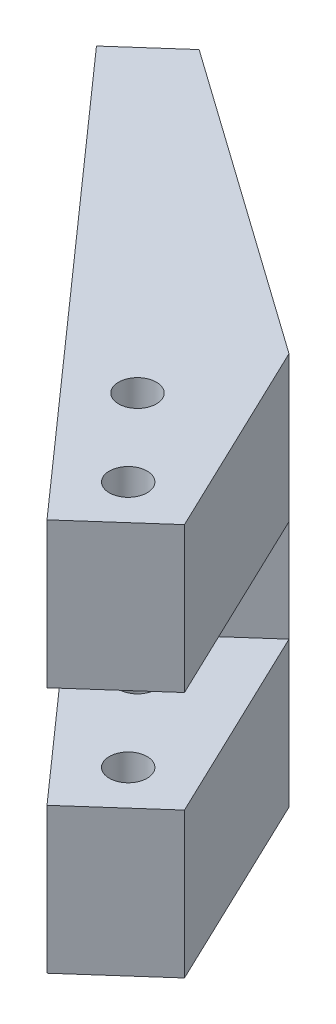
SolidWorks part; units mm, degrees
ref_plane "Front Plane" through (0, 0, 0) normal (0, 0, 1) x (1, 0, 0)
ref_plane "Top Plane" through (0, 0, 0) normal (0, 1, 0) x (1, 0, 0)
ref_plane "Right Plane" through (0, 0, 0) normal (1, 0, 0) x (0, 0, -1)
sketch "Sketch1" plane through (0, 0, 0) normal (0, 1, 0) x (1, 0, 0)
  line L0 (47.5, -78.4427) -> (47.5, -38.4427)
  line L1 (42.5, 50) -> (0, 0)
  line L2 (0, 0) -> (35.1, -73.4224)
  line L3 (47.5, 38.4427) -> (47.5, 50)
  line L4 (42.5, 50) -> (47.5, 50)
  line L6 (35.1, -73.4224) -> (35.1, -93.4427)
  line L8 (37.5, -78.4427) -> (37.5, -93.4427) construction
  line L9 (37.5, -93.4427) -> (47.5, -93.4427)
  line L10 (47.5, -78.4427) -> (47.5, -93.4427)
  line L11 (35.1, -93.4427) -> (37.5, -93.4427)
  line L12 (35.1, -73.4224) -> (37.5, -78.4427) construction
  arc A0 (47.5, 38.4427) -> (47.5, -38.4427) centre (65.622, 0) ccw
  dimension "D1" = 85
  dimension "D2" = 50
  dimension "D3" = 40
  dimension "D4" = 47.5
  dimension "D5" = 10
  dimension "D6" = 5
  dimension "D7" = 65.622
  dimension "D8" = 15
  dimension "D9" = 12.4
extrude "Boss-Extrude1" add sketch "Sketch1" along normal blind 14
sketch "Sketch3" plane through (0, 0, 0) normal (0, -1, 0) x (1, 0, 0)
  line L8 (36.1851, 83.429) -> (36.1851, 109.2435) construction
  line L9 (33.255, 84.4031) -> (36.1851, 92.429)
  line L10 (35.3457, 53.1123) -> (33.255, 84.4031)
  line L11 (46.1351, 70.029) -> (44.8209, 53.0622)
  line L12 (46.1351, 88.029) -> (46.1351, 70.029)
  line L13 (44.8851, 92.429) -> (46.1351, 88.029)
  line L14 (36.1851, 92.429) -> (44.8851, 92.429)
  circle A6 centre (40.0851, 83.429) radius 6.75 construction
  circle A7 centre (40.0851, 83.429) radius 4.125
  circle A8 centre (40.0851, 63.429) radius 1.5 construction
  circle A9 centre (40.0851, 58.929) radius 1.5 construction
  circle A10 centre (40.0851, 53.429) radius 1.5 construction
  arc A11 (44.8209, 53.0622) -> (35.3457, 53.1123) centre (40.0851, 53.429) cw
  point P48 (33.3351, 83.429)
  dimension "D6" = 108.929
  dimension "D7" = 113.429
  dimension "D1" = 3
  dimension "D2" = 40.0851
  dimension "D3" = 47.5
  dimension "D4" = 50
  dimension "D5" = 103.429
extrude "Cut-Extrude1" cut sketch "Sketch3" against normal blind 6
sketch "Sketch5" plane through (0, 6, 0) normal (0, -1, 0) x (1, 0, 0)
  circle A0 centre (40.0851, 63.429) radius 1.125
  circle A1 centre (40.0851, 58.929) radius 1.125
  circle A2 centre (40.0851, 53.429) radius 1.125
  circle A3 centre (40.0851, 63.429) radius 1.5 construction
  circle A4 centre (40.0851, 58.929) radius 1.5 construction
  circle A5 centre (40.0851, 53.429) radius 1.5 construction
  dimension "D1" = 2.25
extrude "Cut-Extrude2" cut sketch "Sketch5" against normal blind 15
fillet "Fillet1" radius 1 14 edges at (47.5, 7, 38.4427) (47.5, 7, -38.4427) (47.5, 7, -50) (42.5, 7, -50) (21.25, 14, -25) (45, 14, -50) (47.5, 14, -44.2214) (23.122, 14, 0) (47.5, 14, 65.9427) (21.25, 0, -25) (45, 0, -50) (47.5, 0, -44.2214) (23.122, 0, 0) (47.5, 0, 65.9427)
sketch "Sketch6" plane through (0, 0, 0) normal (0, -1, 0) x (1, 0, 0)
  line L0 (-40.4586, -20.0772) -> (-49.8876, -23.408)
  line L2 (0, 0) -> (34.1249, 71.3827)
  line L5 (-49.8876, -23.408) -> (34.1249, 71.3827)
  line L6 (-40.4586, -20.0772) -> (-20.5602, 2.374)
  arc A0 (0, 0) -> (-20.5602, 2.374) centre (-20.6309, -88.4563) ccw
  dimension "D1" = 10
  dimension "D2" = 30
  dimension "D3" = 16
extrude "Boss-Extrude3" add sketch "Sketch6" along normal blind 20 and the other way blind 34
sketch "Sketch7" plane through (-16.3209, 0, 14.4651) normal (-0.7484, 0, 0.6633) x (0.6633, 0, 0.7484)
  line L0 (76.0552, 14) -> (29.3477, 14)
  line L1 (76.0552, 0) -> (29.3477, 0)
  line L2 (29.3477, 34) -> (76.0552, 34)
  line L3 (76.0552, 34) -> (76.0552, 14)
  line L4 (29.3477, -20) -> (76.0552, -20)
  line L5 (76.0552, -20) -> (76.0552, 0)
  line L6 (76.0552, 34) -> (-50.6072, 34) construction
  line L7 (76.0552, 34) -> (76.0552, 14) construction
  line L8 (76.0552, 0) -> (76.0552, -20) construction
  line L9 (76.0552, -20) -> (-50.6072, -20) construction
  line L10 (29.3477, 14) -> (29.3477, 34)
  line L11 (29.3477, 0) -> (29.3477, -20)
  line L12 (1.0529, 14) -> (76.0552, 14) construction
extrude "Cut-Extrude3" cut sketch "Sketch7" against normal blind 30
sketch "Sketch10" plane through (0, -20, 0) normal (0, -1, 0) x (1, 0, 0)
  line L1 (-49.8876, -23.408) -> (-42.4038, -30.0408)
  line L2 (-49.8876, -23.408) -> (-16.7236, 14.0107)
  line L3 (-16.7236, 14.0107) -> (0, 0)
  line L4 (-42.4038, -30.0408) -> (0, 0)
  line L7 (3.1449, 36.4281) -> (-49.8876, -23.408) construction
  dimension "D1" = 10
  dimension "D2" = 90
  dimension "D3" = 50
extrude "Boss-Extrude4" add sketch "Sketch10" against normal blind 3
extrude "Boss-Extrude5" add sketch "Sketch10<2>" along normal blind 3 from surface starting at face at (-15.7543, 34, 3.9082)
sketch "Sketch10<2>" plane through (0, -20, 0) normal (0, -1, 0) x (1, 0, 0) same geometry as "Sketch10"
ref_plane "Plane2" through (0, 7, 0) normal (0, -1, 0) x (-1, 0, 0)
sketch "Sketch15" plane through (0, 6, 0) normal (0, -1, 0) x (-1, 0, 0)
  line L1 (-30.98, -71.3827) -> (-57.8606, -71.3827)
  line L2 (-30.98, -71.3827) -> (-30.98, -112.2395)
  line L3 (-30.98, -112.2395) -> (-57.8606, -112.2395)
  line L4 (-57.8606, -71.3827) -> (-57.8606, -112.2395)
extrude "Cut-Extrude5" cut sketch "Sketch15" along normal up to surface (6 mm away) up to face at (40.0851, 0, 87.554)
sketch "Sketch16" plane through (0, 14, 0) normal (0, 1, 0) x (1, 0, 0)
  circle A0 centre (40.0851, -83.429) radius 1.6
  circle A1 centre (40.0851, -63.429) radius 1.125 construction
  dimension "D1" = 20
  dimension "D2" = 3.2
extrude "Cut-Extrude6" cut sketch "Sketch16" against normal up to next
sketch "Sketch17" plane through (0, 7, 0) normal (0, -1, 0) x (-1, 0, 0)
  circle A0 centre (-22.3948, -50.6094) radius 103.4568 construction
sketch "Sketch19" plane through (-16.3209, 0, 14.4651) normal (-0.7484, 0, 0.6633) x (0.6633, 0, 0.7484)
  line L0 (29.3477, 14) -> (76.0552, 14) construction
  line L1 (0, 14) -> (109.6521, 14)
  line L2 (0, 14) -> (0, 0)
  line L3 (0, 0) -> (109.6521, 0)
  line L4 (109.6521, 14) -> (109.6521, 0)
  line L5 (76.0552, 0) -> (29.3477, 0) construction
  line L7 (0, 31) -> (0, 13) construction
extrude "Cut-Extrude7" cut sketch "Sketch19" against normal through all both and the other way through all
sketch "Sketch21" plane through (0, 0, 0) normal (0.9022, 0, -0.4313) x (-0.4313, 0, -0.9022)
  line L1 (-23.655, 14) -> (73.0722, 14)
  line L2 (-23.655, 14) -> (-23.655, 0)
  line L3 (-23.655, 0) -> (73.0722, 0)
  line L4 (73.0722, 14) -> (73.0722, 0)
  line L5 (0, 14) -> (-30.5304, 14) construction
  line L6 (0, 0) -> (-30.5304, 0) construction
  point P6 (0, 0)
extrude "Cut-Extrude8" cut sketch "Sketch21" along normal through all
sketch "Sketch22" plane through (0, -20, 0) normal (0, -1, 0) x (-1, 0, 0)
  line L0 (-3.1449, -36.4281) -> (49.8876, 23.408) construction
  line L2 (0, 0) -> (16.3209, -14.4651) construction
  line L3 (5.7335, -15.1033) -> (-8.7577, -31.4536) construction
  line L4 (-3.1449, -36.4281) -> (-13.1679, -27.5448) construction
  circle A0 centre (5.7335, -15.1033) radius 2.6
  circle A1 centre (-4.2157, -26.3289) radius 2.6
  point P6 (0, 0)
  dimension "D1" = 5.2
  dimension "D4" = 15
  dimension "D2" = 7.5
  dimension "D3" = 7.5
extrude "Cut-Extrude9" cut sketch "Sketch22" against normal through all contours A0 | A1
equation "\"A\"= 20mm"
equation "\"B\"= 3"
equation "\"5.000000mmB\"=5"
